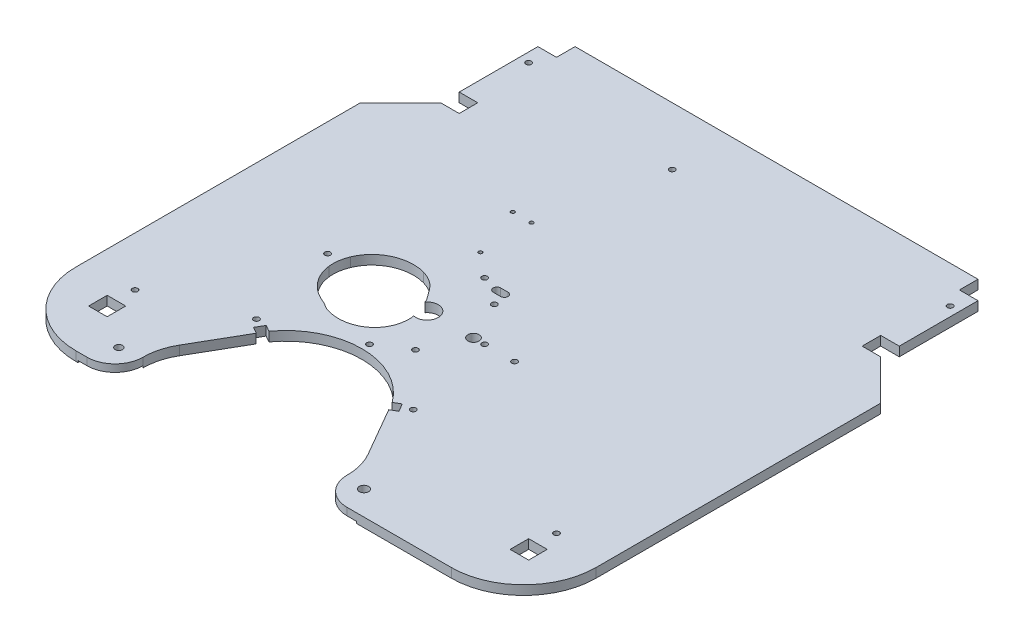
SolidWorks part; units mm, degrees
material "ABS PC"
ref_plane "Plan de face" through (0, 0, 0) normal (0, 0, 1) x (1, 0, 0)
ref_plane "Plan de dessus" through (0, 0, 0) normal (0, 1, 0) x (1, 0, 0)
ref_plane "Plan de droite" through (0, 0, 0) normal (1, 0, 0) x (0, 0, -1)
sketch "Esquisse1" plane through (0, 0, 0) normal (0, 1, 0) x (1, 0, 0)
  line L1 (-140.1, 31.2) -> (140.1, 31.2)
  line L2 (-140.1, 31.2) -> (-140.1, -245.0829)
  line L3 (-140.1, -245.0829) -> (140.1, -245.0829)
  line L4 (140.1, 31.2) -> (140.1, -245.0829)
  line L5 (45, -245.0829) -> (50, -245.0829) construction
  line L6 (-113.5, 31.2) -> (113.5, 31.2) construction
  line L7 (140.1, -4) -> (140.1, 4) construction
  line L8 (-140.1, 4) -> (-140.1, -4) construction
extrude "Boss.-Extru.1" add sketch "Esquisse1" along normal blind 5
sketch "Esquisse2" plane through (0, 0, 0) normal (0, 1, 0) x (1, 0, 0)
  line L3 (-58.1815, -184) -> (-61.6457, -182)
  line L4 (-61.6457, -182) -> (-64.1457, -186.3301)
  line L5 (-64.1457, -186.3301) -> (-60.6815, -188.3301)
  line L7 (-25, -132) -> (-25, -245.0829) construction
  line L8 (-58.1815, -184) -> (-60.6815, -188.3301) construction
  line L9 (-62.6323, -132) -> (62.6323, -132) construction
  line L10 (-25, -62.6323) -> (-25, 62.6323) construction
  line L11 (-60.6815, -188.3301) -> (-75.8539, -214.6094)
  line L13 (-58.1815, -184) -> (-54.7174, -186) construction
  line L14 (-25, -168.5125) -> (-25, -231.5125) construction
  line L16 (140.1, -245.0829) -> (-140.1, -245.0829) construction
  line L17 (-140.1, -245.0829) -> (140.1, -245.0829) construction
  line L18 (8.1815, -184) -> (4.7174, -186) construction
  line L20 (8.1815, -184) -> (10.6815, -188.3301) construction
  line L21 (10.6815, -188.3301) -> (25.8539, -214.6094)
  line L22 (14.1457, -186.3301) -> (10.6815, -188.3301)
  line L23 (11.6457, -182) -> (14.1457, -186.3301)
  line L24 (8.1815, -184) -> (11.6457, -182)
  line L25 (-62.8957, -184.1651) -> (-67.2258, -181.6651) construction
  line L26 (-95, -245.0829) -> (45, -245.0829)
  arc A1 (8.1815, -184) -> (-58.1815, -184) centre (-25, -208.0829) ccw
  arc A2 (-95, -245.0829) -> (-80, -230.0829) centre (-95, -230.0829) ccw
  arc A3 (-95, -245.0829) -> (-86.2863, -217.8734) centre (-95, -230.0829) ccw construction
  arc A4 (-80, -230.0829) -> (-75.8539, -214.6094) centre (-49.0531, -230.0829) cw
  arc A5 (30, -230.0829) -> (25.8539, -214.6094) centre (-0.9469, -230.0829) ccw
  arc A6 (45, -245.0829) -> (30, -230.0829) centre (45, -230.0829) cw
  circle A8 centre (-67.2258, -181.6651) radius 1.5
  circle A10 centre (17.2258, -181.6651) radius 1.5
  dimension "D4" = 41
  dimension "D8" = 5
  dimension "D9" = 3
  dimension "D1" = 4
  dimension "D2" = 52
  dimension "D3" = 37
  dimension "D5" = 90
  dimension "D6" = 5
  dimension "D7" = 30
extrude "Enlèv. mat.-Extru.2" cut sketch "Esquisse2" along normal through all
sketch "Esquisse3" plane through (0, 5, 0) normal (0, 1, 0) x (1, 0, 0)
  line L0 (-30.2322, -127.0569) -> (-26.1247, -139.1312)
  spline S0 degree 3 poles (-1524.8341, -1452.5331) (-200.5452, -428.348) (10.8704, -188.1918) (-31.7245, -126.6315) (-31.8941, -126.3945) (-32.4016, -125.6823) (-32.7422, -125.2091) (-58.8228, -89.2587) (-90.5389, -57.2295) (-1659.8243, -1285.8652) knots -31.850463 -31.850463 -31.850463 -31.850463 0.125 0.125 0.25 0.25 0.5 0.5 19.29405 19.29405 19.29405 19.29405 only from (-31.0727, -127.5986) to (-35.1803, -121.9365)
  spline S1 degree 3 poles (364.0931, 1835.8687) (-340.6814, -513.038) (-113.9465, -84.5198) (-40.8811, -117.114) (-40.044, -117.5631) (-38.8602, -118.3319) (-38.4767, -118.6044) (-37.7343, -119.185) (-37.3745, -119.4945) (-14.0434, -142.3698) (-68.5996, -233.8683) (1519.3139, 1134.9781) knots -20.904049 -20.904049 -20.904049 -20.904049 0.25 0.25 0.5 0.5 0.625 0.625 0.75 0.75 9.313235 9.313235 9.313235 9.313235 only from (-44.3577, -115.7789) to (-35.1803, -121.9365)
  spline S2 degree 3 poles (-1305.5548, -1643.1059) (8.9079, -543.4216) (30.3671, -122.9167) (-49.4488, -114.9227) (-50.737, -114.9092) (-52.6603, -115.0546) (-53.2999, -115.1309) (-54.576, -115.34) (-55.2153, -115.474) (-57.0956, -115.9555) (-58.3066, -116.3821) (-60.0589, -117.1815) (-60.6325, -117.4741) (-61.7574, -118.1146) (-62.3096, -118.4643) (-63.8985, -119.5739) (-64.8782, -120.402) (-66.225, -121.7806) (-66.6531, -122.2633) (-67.2625, -123.0236) (-67.4604, -123.2834) (-67.8414, -123.8087) (-68.025, -124.075) (-110.7871, -189.31) (235.2262, -459.8979) (1576.8374, -1257.2957) knots -7.457247 -7.457247 -7.457247 -7.457247 0.125 0.125 0.25 0.25 0.3125 0.3125 0.375 0.375 0.5 0.5 0.5625 0.5625 0.625 0.625 0.75 0.75 0.8125 0.8125 0.84375 0.84375 0.875 0.875 8.398041 8.398041 8.398041 8.398041 only from (-44.3577, -115.7789) to (-70, -127.755)
  spline S3 degree 3 poles (-47.9813, 1856.8275) (125.181, -244.0769) (-72.0855, -184.256) (-71.4642, -134.1161) (-71.4011, -133.3001) (-71.1736, -131.6775) (-71.0075, -130.8697) (-17.8642, 63.8002) (2969.019, -622.8948) (-1651.8454, 973.7425) knots -14.76961 -14.76961 -14.76961 -14.76961 0.25 0.25 0.5 0.5 0.75 0.75 62.135828 62.135828 62.135828 62.135828 only from (-71.343, -137.3985) to (-70, -127.755)
  spline S4 degree 3 poles (-2001.2881, 32.8008) (2629.6596, 821.1196) (-125.1007, 42.2047) (-70.5251, -141.1324) (-70.3458, -141.6526) (-69.9413, -142.6832) (-69.718, -143.1876) (-68.9919, -144.665) (-68.4298, -145.6034) (-67.479, -146.9469) (-67.1435, -147.384) (-66.4359, -148.235) (-66.0677, -148.6441) (-64.924, -149.8269) (-64.1096, -150.5562) (-62.7975, -151.5474) (-62.3475, -151.8633) (-61.6568, -152.3195) (-61.425, -152.47) (-60.9583, -152.7645) (-60.7209, -152.9041) (-60.001, -153.3084) (-59.5102, -153.5575) (-58.5114, -154.0234) (-58.0032, -154.2398) (-57.2409, -154.5624) (-56.9867, -154.6699) (-56.4801, -154.8889) (-56.2268, -154.9985) (-55.7258, -155.2315) (-55.4826, -155.3662) (-43.6824, -163.0213) (-44.4169, -201.2221) (725.64, 1684.5228) knots -21.636057 -21.636057 -21.636057 -21.636057 0.125 0.125 0.1875 0.1875 0.25 0.25 0.375 0.375 0.4375 0.4375 0.5 0.5 0.625 0.625 0.6875 0.6875 0.71875 0.71875 0.75 0.75 0.8125 0.8125 0.875 0.875 0.90625 0.90625 0.9375 0.9375 0.96875 0.96875 2.500832 2.500832 2.500832 2.500832 only from (-71.343, -137.3985) to (-54.5478, -156)
  spline S5 degree 3 poles (-1738.4139, 892.0597) (140.9741, 43.0874) (2.9113, -175.9233) (-52.26, -157.2053) (-52.4819, -157.1257) (-52.8129, -157.0004) (-52.9231, -156.9582) (-53.1393, -156.8624) (-53.2451, -156.8096) (-53.557, -156.6406) (-53.7605, -156.5209) (-66.1987, -148.6858) (-58.0496, -108.9252) (-1163.5294, -1819.9055) knots -30.265211 -30.265211 -30.265211 -30.265211 0.5 0.5 0.625 0.625 0.6875 0.6875 0.75 0.75 0.875 0.875 8.537384 8.537384 8.537384 8.537384 only from (-49.3008, -158) to (-54.5478, -156)
  spline S6 degree 3 poles (-1949.1275, 426.9773) (43.5324, -0.0898) (1.2961, -154.0463) (-44.2435, -158.3269) (-44.8765, -158.3561) (-46.1445, -158.356) (-46.7811, -158.3264) (-118.6227, -151.5571) (-143.9564, 223.9249) (-15.0957, 1838.9163) knots -17.515041 -17.515041 -17.515041 -17.515041 0.25 0.25 0.5 0.5 0.75 0.75 28.888572 28.888572 28.888572 28.888572 only from (-41.7229, -158) to (-49.3008, -158)
  spline S7 degree 3 poles (-1666.5719, -1296.3963) (-65.6297, 95.6251) (7.8642, -129.1094) (-36.0016, -155.9655) (-36.6799, -156.3213) (-38.0707, -156.9471) (-38.7813, -157.2165) (-86.4686, -172.17) (-201.3678, -13.098) (1712.2684, 789.9411) knots -16.36827 -16.36827 -16.36827 -16.36827 0.25 0.25 0.5 0.5 0.75 0.75 16.93969 16.93969 16.93969 16.93969 only from (-33.4851, -154.245) to (-41.7229, -158)
  spline S8 degree 3 poles (1046.2165, -1823.3231) (-784.0739, 385.5367) (-101.1747, -227.9262) (-31.3895, -152.2364) (-31.1171, -151.9192) (-30.5932, -151.2613) (-30.343, -150.9217) (-29.6368, -149.8847) (-29.2193, -149.1653) (-28.6747, -148.043) (-28.5063, -147.6619) (-15.3248, -114.6524) (-97.8799, -22.7511) (-912.2607, -1937.4947) knots -30.529041 -30.529041 -30.529041 -30.529041 0.25 0.25 0.375 0.375 0.5 0.5 0.75 0.75 0.875 0.875 11.380924 11.380924 11.380924 11.380924 only from (-33.4851, -154.245) to (-27.928, -146.0877)
  spline S9 degree 3 poles (-89.1423, -2133.2638) (-210.1557, -2.8223) (-21.556, -93.2311) (-33.3079, -196.0579) (-262.9799, -213.9602) (-2020.0373, 10.4615) knots -20.97712 -20.97712 -20.97712 -20.97712 0.5 0.5 23.678782 23.678782 23.678782 23.678782 only from (-27.1228, -139.1933) to (-27.928, -146.0877)
  spline S10 degree 3 poles (-27.1228, -139.1933) (-27.0502, -140.3605) (-27.0765, -141.534) (-27.3396, -143.8367) (-27.5752, -144.9715) (-27.928, -146.0877) knots 0 0 0 0 0.5 0.5 1 1 1 1 construction
  spline S11 degree 3 poles (-33.4851, -154.245) (-32.8413, -153.7217) (-32.2363, -153.1548) (-31.3895, -152.2364) (-31.1171, -151.9192) (-30.5932, -151.2613) (-30.343, -150.9217) (-29.6368, -149.8847) (-29.2193, -149.1653) (-28.6747, -148.043) (-28.5063, -147.6619) (-28.1963, -146.8857) (-28.0548, -146.4892) (-27.928, -146.0877) knots 0 0 0 0 0.25 0.25 0.375 0.375 0.5 0.5 0.75 0.75 0.875 0.875 1 1 1 1 construction
  spline S12 degree 3 poles (-33.4851, -154.245) (-34.0776, -154.7266) (-34.7013, -155.1695) (-36.0016, -155.9655) (-36.6799, -156.3213) (-38.0707, -156.9471) (-38.7813, -157.2165) (-40.2317, -157.6713) (-40.9731, -157.8572) (-41.7229, -158) knots 0 0 0 0 0.25 0.25 0.5 0.5 0.75 0.75 1 1 1 1 construction
  spline S13 degree 3 poles (-41.7229, -158) (-42.3482, -158.1191) (-42.9796, -158.2081) (-44.2435, -158.3269) (-44.8765, -158.3561) (-46.1445, -158.356) (-46.7811, -158.3264) (-48.0464, -158.2072) (-48.6755, -158.1184) (-49.3008, -158) knots 0 0 0 0 0.25 0.25 0.5 0.5 0.75 0.75 1 1 1 1 construction
  spline S14 degree 3 poles (-49.3008, -158) (-50.2287, -157.8243) (-51.1437, -157.584) (-52.26, -157.2053) (-52.4819, -157.1257) (-52.8129, -157.0004) (-52.9231, -156.9582) (-53.1393, -156.8624) (-53.2451, -156.8096) (-53.557, -156.6406) (-53.7605, -156.5209) (-54.1598, -156.2694) (-54.3541, -156.1351) (-54.5478, -156) knots 0 0 0 0 0.5 0.5 0.625 0.625 0.6875 0.6875 0.75 0.75 0.875 0.875 1 1 1 1 construction
  spline S15 degree 3 poles (-71.343, -137.3985) (-71.2139, -138.4875) (-70.994, -139.5573) (-70.5251, -141.1324) (-70.3458, -141.6526) (-69.9413, -142.6832) (-69.718, -143.1876) (-68.9919, -144.665) (-68.4298, -145.6034) (-67.479, -146.9469) (-67.1435, -147.384) (-66.4359, -148.235) (-66.0677, -148.6441) (-64.924, -149.8269) (-64.1096, -150.5562) (-62.7975, -151.5474) (-62.3475, -151.8633) (-61.6568, -152.3195) (-61.425, -152.47) (-60.9583, -152.7645) (-60.7209, -152.9041) (-60.001, -153.3084) (-59.5102, -153.5575) (-58.5114, -154.0234) (-58.0032, -154.2398) (-57.2409, -154.5624) (-56.9867, -154.6699) (-56.4801, -154.8889) (-56.2268, -154.9985) (-55.7258, -155.2315) (-55.4826, -155.3662) (-55.0108, -155.6722) (-54.7801, -155.838) (-54.5478, -156) knots 0 0 0 0 0.125 0.125 0.1875 0.1875 0.25 0.25 0.375 0.375 0.4375 0.4375 0.5 0.5 0.625 0.625 0.6875 0.6875 0.71875 0.71875 0.75 0.75 0.8125 0.8125 0.875 0.875 0.90625 0.90625 0.9375 0.9375 0.96875 0.96875 1 1 1 1 construction
  spline S16 degree 3 poles (-71.343, -137.3985) (-71.4399, -136.5817) (-71.4845, -135.7579) (-71.4642, -134.1161) (-71.4011, -133.3001) (-71.1736, -131.6775) (-71.0075, -130.8697) (-70.5764, -129.2906) (-70.3122, -128.5156) (-70, -127.755) knots 0 0 0 0 0.25 0.25 0.5 0.5 0.75 0.75 1 1 1 1 construction
  spline S17 degree 3 poles (-44.3577, -115.7789) (-45.5925, -115.4238) (-46.8598, -115.182) (-49.4488, -114.9227) (-50.737, -114.9092) (-52.6603, -115.0546) (-53.2999, -115.1309) (-54.576, -115.34) (-55.2153, -115.474) (-57.0956, -115.9555) (-58.3066, -116.3821) (-60.0589, -117.1815) (-60.6325, -117.4741) (-61.7574, -118.1146) (-62.3096, -118.4643) (-63.8985, -119.5739) (-64.8782, -120.402) (-66.225, -121.7806) (-66.6531, -122.2633) (-67.2625, -123.0236) (-67.4604, -123.2834) (-67.8414, -123.8087) (-68.025, -124.075) (-68.9095, -125.4243) (-69.5098, -126.5605) (-70, -127.755) knots 0 0 0 0 0.125 0.125 0.25 0.25 0.3125 0.3125 0.375 0.375 0.5 0.5 0.5625 0.5625 0.625 0.625 0.75 0.75 0.8125 0.8125 0.84375 0.84375 0.875 0.875 1 1 1 1 construction
  spline S18 degree 3 poles (-44.3577, -115.7789) (-43.4629, -116.0363) (-42.5879, -116.3526) (-40.8811, -117.114) (-40.044, -117.5631) (-38.8602, -118.3319) (-38.4767, -118.6044) (-37.7343, -119.185) (-37.3745, -119.4945) (-36.3675, -120.4818) (-35.7623, -121.1988) (-35.1803, -121.9365) knots 0 0 0 0 0.25 0.25 0.5 0.5 0.625 0.625 0.75 0.75 1 1 1 1 construction
  spline S19 degree 3 poles (-31.0727, -127.5986) (-31.2308, -127.3534) (-31.3928, -127.111) (-31.7245, -126.6315) (-31.8941, -126.3945) (-32.4016, -125.6823) (-32.7422, -125.2091) (-33.7693, -123.7933) (-34.4583, -122.8518) (-35.1803, -121.9365) knots 0 0 0 0 0.125 0.125 0.25 0.25 0.5 0.5 1 1 1 1 construction
  spline S20 degree 1 poles (-26.1247, -139.1312) (-26.9745, -146.389) knots 0 0 1 1 construction
  spline S21 degree 1 poles (-32.8544, -155.021) (-26.9745, -146.389) knots 0 0 1 1 construction
  spline S22 degree 1 poles (-32.8544, -155.021) (-41.5359, -158.9824) knots 0 0 1 1 construction
  spline S23 degree 1 poles (-41.5359, -158.9824) (-49.4869, -158.9825) knots 0 0 1 1 construction
  spline S24 degree 1 poles (-49.4869, -158.9825) (-55.1198, -156.8203) knots 0 0 1 1 construction
  spline S25 degree 1 poles (-72.336, -137.5162) (-55.1198, -156.8203) knots 0 0 1 1 construction
  spline S26 degree 1 poles (-72.336, -137.5162) (-70.9251, -127.3753) knots 0 0 1 1 construction
  spline S27 degree 1 poles (-44.0813, -114.8179) (-70.9251, -127.3753) knots 0 0 1 1 construction
  spline S28 degree 1 poles (-44.0813, -114.8179) (-34.3952, -121.3172) knots 0 0 1 1 construction
  spline S29 degree 1 poles (-30.2322, -127.0569) (-34.3952, -121.3172) knots 0 0 1 1 construction
  spline S30 degree 3 poles (-26.1247, -139.1312) (-25.9734, -141.5623) (-26.2405, -144.0664) (-26.9745, -146.389) knots 0 0 0 0 1 1 1 1
  spline S31 degree 3 poles (-26.9745, -146.389) (-27.2409, -147.2323) (-27.9017, -148.8872) (-29.2221, -151.1686) (-30.8961, -153.272) (-32.1739, -154.4679) (-32.8544, -155.021) knots 0 0 0 0 0.25 0.5 0.75 1 1 1 1
  spline S32 degree 3 poles (-32.8544, -155.021) (-34.1022, -156.0352) (-36.8953, -157.7328) (-39.967, -158.6836) (-41.5359, -158.9824) knots 0 0 0 0 0.5 1 1 1 1
  spline S33 degree 3 poles (-41.5359, -158.9824) (-44.1394, -159.4781) (-46.8829, -159.4757) (-49.4869, -158.9825) knots 0 0 0 0 1 1 1 1
  spline S34 degree 3 poles (-49.4869, -158.9825) (-49.9734, -158.8904) (-50.9415, -158.6718) (-52.0056, -158.3522) (-52.7107, -158.1061) (-53.0491, -157.981) (-53.4323, -157.8343) (-53.8396, -157.6291) (-54.1621, -157.4443) (-54.4936, -157.2441) (-54.8226, -157.0271) (-55.0192, -156.8904) (-55.1198, -156.8203) knots 0 0 0 0 0.25 0.5 0.5625 0.625 0.6875 0.75 0.8125 0.875 0.9375 1 1 1 1
  spline S35 degree 3 poles (-55.1198, -156.8203) (-55.3426, -156.6649) (-55.8212, -156.3208) (-56.3578, -156.0288) (-57.1358, -155.6943) (-58.1278, -155.2724) (-59.4415, -154.7137) (-60.7152, -154.07) (-61.7361, -153.4634) (-62.6711, -152.8531) (-64.3255, -151.7044) (-66.4613, -149.7979) (-68.6889, -147.1234) (-71.0457, -143.1846) (-72.0656, -139.797) (-72.336, -137.5162) knots 0 0 0 0 0.03125 0.0625 0.09375 0.125 0.1875 0.25 0.28125 0.3125 0.375 0.5 0.625 0.75 1 1 1 1
  spline S36 degree 3 poles (-72.336, -137.5162) (-72.5389, -135.806) (-72.4971, -132.3145) (-71.5776, -128.965) (-70.9251, -127.3753) knots 0 0 0 0 0.5 1 1 1 1
  spline S37 degree 3 poles (-70.9251, -127.3753) (-70.4131, -126.1277) (-69.1525, -123.7337) (-66.5762, -120.5203) (-63.4912, -117.9189) (-59.9299, -115.8897) (-56.1282, -114.5536) (-52.0981, -113.8904) (-48.0468, -113.9388) (-45.3772, -114.4451) (-44.0813, -114.8179) knots 0 0 0 0 0.125 0.25 0.375 0.5 0.625 0.75 0.875 1 1 1 1
  spline S38 degree 3 poles (-44.0813, -114.8179) (-43.1424, -115.0879) (-41.3106, -115.748) (-39.1035, -116.9336) (-37.4821, -118.0811) (-36.3107, -119.0968) (-35.3076, -120.1888) (-34.6959, -120.936) (-34.3952, -121.3172) knots 0 0 0 0 0.25 0.5 0.625 0.75 0.875 1 1 1 1
  spline S39 degree 3 poles (-34.3952, -121.3172) (-33.6647, -122.2432) (-32.6101, -123.6823) (-31.2535, -125.565) (-30.5565, -126.5538) (-30.2322, -127.0569) knots 0 0 0 0 0.5 0.75 1 1 1 1
  dimension "D1" = 1
extrude "Enlèv. mat.-Extru.3" cut sketch "Esquisse3" against normal through all
sketch "Esquisse4" plane through (0, 5, 0) normal (0, 1, 0) x (1, 0, 0)
  circle A0 centre (-48.2, -62.65) radius 1
  circle A1 centre (-38.1, -62.65) radius 1
  circle A2 centre (-38.1, -90.25) radius 1
  dimension "D1" = 2
extrude "Enlèv. mat.-Extru.4" cut sketch "Esquisse4" against normal through all
sketch "Esquisse5" plane through (0, 5, 0) normal (0, 1, 0) x (1, 0, 0)
  circle A0 centre (22.1224, -132) radius 1.5
  circle A1 centre (-10.0508, -153.25) radius 1.5
  circle A2 centre (-25, -163) radius 1.5
  circle A3 centre (-10.0508, -110.75) radius 1.5
  circle A4 centre (-25, -101) radius 1.5
  circle A5 centre (-78.6, -132) radius 1.5
  circle A6 centre (6, -132) radius 1.5 construction
  circle A7 centre (6, -132) radius 1.5
  circle A8 centre (0, -132) radius 3
  arc A9 (1.5616, -134.5616) -> (1.5616, -129.4384) centre (0, -132) ccw construction
  dimension "D1" = 3
extrude "Enlèv. mat.-Extru.5" cut sketch "Esquisse5" against normal through all
sketch "Esquisse6" plane through (0, 5, 0) normal (0, 1, 0) x (1, 0, 0)
  circle A0 centre (-25, -132) radius 6
  circle A1 centre (-25, -132) radius 5.4 construction
  dimension "D1" = 12
extrude "Enlèv. mat.-Extru.6" cut sketch "Esquisse6" against normal through all
sketch "Esquisse7" plane through (0, 5, 0) normal (0, 1, 0) x (1, 0, 0)
  line L1 (-16, -103.4) -> (-12, -103.4) construction
  line L2 (-16, -101.4) -> (-12, -101.4)
  line L3 (-16, -105.4) -> (-12, -105.4)
  arc A0 (-16, -101.4) -> (-16, -105.4) centre (-16, -103.4) ccw
  arc A6 (-12, -105.4) -> (-12, -101.4) centre (-12, -103.4) ccw
  arc A7 (-11.4091, -103.2958) -> (-12.5909, -103.2958) centre (-12, -103.4) ccw construction
  arc A9 (-15.4091, -103.2958) -> (-16.5909, -103.2958) centre (-16, -103.4) ccw construction
  point P2 (-14, -103.4)
  dimension "D1" = 4
extrude "Enlèv. mat.-Extru.7" cut sketch "Esquisse7" against normal through all
sketch "Esquisse8" plane through (0, 5, 0) normal (0, 1, 0) x (1, 0, 0)
  line L0 (140.1, -245.0829) -> (140.1, 31.2) construction
  line L1 (101.1, -245.0829) -> (140.1, -245.0829)
  line L2 (140.1, -245.0829) -> (140.1, -206.0829)
  line L3 (-140.1, -245.0829) -> (-140.1, -206.0829)
  line L4 (-140.1, 31.2) -> (-140.1, -245.0829) construction
  line L5 (-140.1, -245.0829) -> (-95, -245.0829) construction
  line L6 (-101.1, -245.0829) -> (-140.1, -245.0829)
  arc A0 (140.1, -206.0829) -> (101.1, -245.0829) centre (101.1, -206.0829) cw
  arc A1 (-140.1, -206.0829) -> (-101.1, -245.0829) centre (-101.1, -206.0829) ccw
extrude "Enlèv. mat.-Extru.8" cut sketch "Esquisse8" against normal through all
sketch "Esquisse9" plane through (0, 5, 0) normal (0, 1, 0) x (1, 0, 0)
  line L0 (-108.5, 21.2) -> (-118.5, 21.2) construction
  line L1 (-108.5, 21.2) -> (-108.5, 31.2) construction
  line L2 (-108.5, -31.2) -> (-108.5, -21.2) construction
  line L3 (-108.5, -21.2) -> (-118.5, -21.2) construction
  line L4 (-108.5, -31.2) -> (-118.5, -31.2) construction
  line L5 (-108.5, 21.2) -> (-118.5, 21.2)
  line L6 (-108.5, 21.2) -> (-108.5, 31.2)
  line L7 (-108.5, -31.2) -> (-108.5, -21.2)
  line L8 (-108.5, -21.2) -> (-118.5, -21.2)
  line L9 (-108.5, -31.2) -> (-118.5, -31.2)
  line L10 (-118.5, -21.2) -> (-118.5, 21.2)
  line L11 (-118.5, -31.2) -> (-140.1, -52.8)
  line L12 (-140.1, 31.2) -> (-140.1, -206.0829) construction
  line L13 (-140.1, -52.8) -> (-140.1, 31.2)
  line L14 (-140.1, 31.2) -> (-108.5, 31.2)
  line L15 (0, 0) -> (0, 79.4635) construction
  line L16 (140.1, 31.2) -> (108.5, 31.2)
  line L17 (140.1, -52.8) -> (140.1, 31.2)
  line L18 (118.5, -31.2) -> (140.1, -52.8)
  line L19 (118.5, -21.2) -> (118.5, 21.2)
  line L20 (108.5, -31.2) -> (118.5, -31.2)
  line L21 (108.5, -21.2) -> (118.5, -21.2)
  line L22 (108.5, -31.2) -> (108.5, -21.2)
  line L23 (108.5, 21.2) -> (108.5, 31.2)
  line L24 (108.5, 21.2) -> (118.5, 21.2)
  dimension "D1" = 45
extrude "Enlèv. mat.-Extru.9" cut sketch "Esquisse9" against normal through all
sketch "Esquisse10" plane through (0, 0, 0) normal (0, -1, 0) x (1, 0, 0)
  line L1 (50, 242.0829) -> (50, 245.0829) construction
  line L2 (50, 245.0829) -> (45, 245.0829) construction
  line L3 (45, 242.0829) -> (50, 242.0829) construction
  line L5 (50, 242.0829) -> (50, 245.0829)
  line L6 (50, 245.0829) -> (45, 245.0829)
  line L7 (45, 242.0829) -> (50, 242.0829)
  line L9 (-88.029, 220.3153) -> (-86.2863, 217.8734)
  line L10 (-95, 245.0829) -> (-95, 242.0829)
  line L15 (-95, 242.0829) -> (-95, 245.0829)
  line L16 (-95, 245.0829) -> (-100, 245.0829)
  line L17 (-100, 245.0829) -> (-100, 242.0829)
  line L18 (-100, 242.0829) -> (-95, 242.0829)
  line L20 (-95, 245.0829) -> (-100, 245.0829)
  line L21 (-100, 245.0829) -> (-100, 242.0829)
  line L22 (-100, 242.0829) -> (-95, 242.0829)
  arc A0 (-88.029, 220.3153) -> (-25, 23.5) centre (-25, 132) ccw construction
  arc A1 (-86.2863, 217.8734) -> (-25, 26.5) centre (-25, 132) ccw construction
  arc A2 (-25, 26.5) -> (36.2863, 217.8734) centre (-25, 132) ccw construction
  arc A3 (-25, 23.5) -> (38.029, 220.3153) centre (-25, 132) ccw construction
  arc A4 (-88.029, 220.3153) -> (-25, 23.5) centre (-25, 132) ccw
  arc A5 (-86.2863, 217.8734) -> (-25, 26.5) centre (-25, 132) ccw
  arc A6 (-25, 26.5) -> (36.2863, 217.8734) centre (-25, 132) ccw
  arc A7 (-25, 23.5) -> (38.029, 220.3153) centre (-25, 132) ccw
  arc A8 (45, 245.0829) -> (36.2863, 217.8734) centre (45, 230.0829) ccw construction
  arc A9 (45, 242.0829) -> (38.029, 220.3153) centre (45, 230.0829) ccw construction
  arc A10 (45, 245.0829) -> (36.2863, 217.8734) centre (45, 230.0829) ccw
  arc A11 (45, 242.0829) -> (38.029, 220.3153) centre (45, 230.0829) ccw
  arc A14 (-86.2863, 217.8734) -> (-95, 245.0829) centre (-95, 230.0829) ccw
  arc A15 (-88.029, 220.3153) -> (-95, 242.0829) centre (-95, 230.0829) ccw
  arc A16 (-86.2863, 217.8734) -> (-95, 245.0829) centre (-95, 230.0829) ccw
  arc A17 (-88.029, 220.3153) -> (-95, 242.0829) centre (-95, 230.0829) ccw
  dimension "D1" = 0
  dimension "D2" = 0
extrude "Enlèv. mat.-Extru.10" cut sketch "Esquisse10" against normal blind 1
sketch "Esquisse11" plane through (0, 5, 0) normal (0, 1, 0) x (1, 0, 0)
  line L4 (-118.5, -210.8) -> (-118.5, -220.8)
  line L5 (-108.5, -210.8) -> (-118.5, -210.8)
  line L6 (-108.5, -220.8) -> (-108.5, -210.8)
  line L7 (-118.5, -220.8) -> (-108.5, -220.8)
  line L8 (-118.5, -210.8) -> (-118.5, -220.8)
  line L9 (-108.5, -210.8) -> (-118.5, -210.8)
  line L10 (-108.5, -220.8) -> (-108.5, -210.8)
  line L11 (-118.5, -220.8) -> (-108.5, -220.8)
  line L12 (108.5, -210.8) -> (108.5, -220.8)
  line L13 (118.5, -210.8) -> (108.5, -210.8)
  line L14 (118.5, -220.8) -> (118.5, -210.8)
  line L15 (108.5, -220.8) -> (118.5, -220.8)
  line L16 (108.5, -210.8) -> (108.5, -220.8)
  line L17 (118.5, -210.8) -> (108.5, -210.8)
  line L18 (118.5, -220.8) -> (118.5, -210.8)
  line L19 (108.5, -220.8) -> (118.5, -220.8)
  dimension "D1" = 0
  dimension "D2" = 0
extrude "Enlèv. mat.-Extru.11" cut sketch "Esquisse11" against normal through all
sketch "Esquisse12" plane through (0, 5, 0) normal (0, 1, 0) x (1, 0, 0)
  circle A0 centre (41, -232) radius 2.5 construction
  circle A1 centre (41, -232) radius 2.5
  circle A2 centre (-91, -232) radius 2 construction
  circle A3 centre (-91, -232) radius 2
extrude "Enlèv. mat.-Extru.12" cut sketch "Esquisse12" against normal through all
sketch "Esquisse13" plane through (0, 5, 0) normal (0, 1, 0) x (1, 0, 0)
  circle A0 centre (-113.5, -200.8) radius 1.5
  circle A1 centre (-113.5, 11.2) radius 1.5
  circle A2 centre (-113.5, 11.2) radius 1.525 construction
  circle A3 centre (-113.5, -200.8) radius 1.525 construction
  circle A4 centre (113.5, 11.2) radius 1.5
  circle A5 centre (113.5, -200.8) radius 1.5
  circle A6 centre (113.5, -200.8) radius 1.25 construction
  circle A7 centre (-25, 0) radius 1.5
  circle A9 centre (-25, 0) radius 1.5 construction
  dimension "D1" = 3
extrude "Enlèv. mat.-Extru.15" cut sketch "Esquisse13" against normal through all
